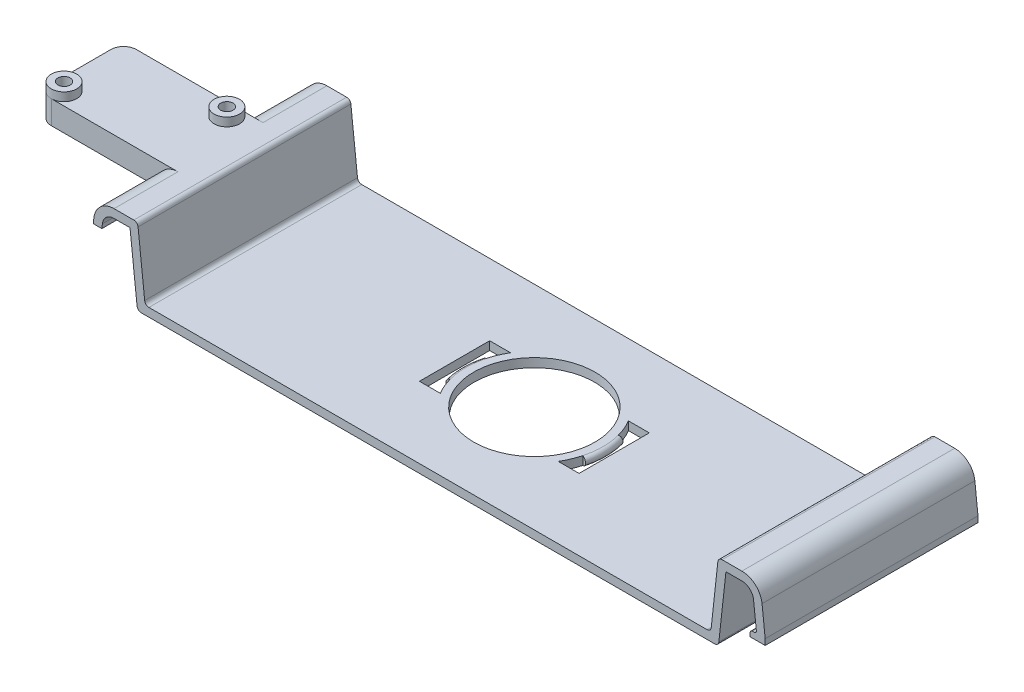
SolidWorks part; units mm, degrees
ref_plane "Front Plane" through (0, 0, 0) normal (0, 0, 1) x (1, 0, 0)
ref_plane "Top Plane" through (0, 0, 0) normal (0, 1, 0) x (1, 0, 0)
ref_plane "Right Plane" through (0, 0, 0) normal (1, 0, 0) x (0, 0, -1)
sketch "Sketch1" plane through (0, 0, 0) normal (0, 0, 1) x (1, 0, 0)
  line L0 (0, 0) -> (-68.25, 0)
  line L1 (55, 0) -> (-55, 0) construction
  line L2 (-68.25, 0) -> (-70, 16)
  line L3 (-70, 16) -> (-73.75, 16)
  line L4 (-76.5, 13.5344) -> (-77.2147, 7)
  line L5 (0, 121.5879) -> (0, -176.7116) construction
  line L6 (0, -55) -> (0, 55) construction
  line L7 (-77.2147, 7) -> (-77.9803, 0) construction
  line L8 (-77.2147, 7) -> (-69.0156, 7) construction
  line L9 (-77.9803, 0) -> (-68.25, 0) construction
  line L10 (0, 2) -> (-66.4568, 2)
  line L11 (-66.4568, 2) -> (-68.2068, 18)
  line L12 (-68.2068, 18) -> (-73.75, 18)
  line L13 (-78.4881, 13.7518) -> (-79.2028, 7.2175)
  line L14 (0, 0) -> (0, 2)
  line L15 (-77.2147, 7) -> (-79.2028, 7.2175)
  arc A0 (-73.75, 16) -> (-76.5, 13.5344) centre (-73.75, 13.2336) ccw
  arc A1 (-73.75, 18) -> (-78.4881, 13.7518) centre (-73.75, 13.2336) ccw
  point P14 (-73.1152, 0)
  point P17 (-73.1152, 7)
  dimension "D1" = 140
  dimension "D2" = 136.5
  dimension "D3" = 16
  dimension "D4" = 3.75
  dimension "D5" = 9
  dimension "D6" = 6.5
  dimension "D7" = 2
extrude "Boss-Extrude1" add sketch "Sketch1" along normal mid plane 50
mirror "Mirror1" about plane through (0, 0, 25) normal (-1, 0, 0) of "Boss-Extrude1"
sketch "Sketch2" plane through (0, 2, 0) normal (0, 1, 0) x (1, 0, 0)
  circle A0 centre (0, 0) radius 14.25
  dimension "D1" = 28.5
extrude "Cut-Extrude1" cut sketch "Sketch2" against normal blind 50 draft 3
sketch "Sketch3" plane through (0, 2, 0) normal (0, 1, 0) x (1, 0, 0)
  line L0 (-18.75, 8.25) -> (-18.75, -8.25)
  line L1 (-18.75, 8.25) -> (-13.8547, 8.25)
  line L3 (-18.75, -8.25) -> (-13.8547, -8.25)
  line L5 (-18.75, 8.25) -> (18.75, -8.25) construction
  line L6 (-18.75, -8.25) -> (-14.7595, -6.4942) construction
  line L7 (18.75, 8.25) -> (18.75, -8.25)
  line L8 (-13.8547, -8.25) -> (13.8547, -8.25) construction
  line L9 (13.8547, -8.25) -> (18.75, -8.25)
  line L10 (-14.7595, -6.4942) -> (0, 0) construction
  line L11 (0, 0) -> (18.75, 8.25) construction
  line L12 (-13.8547, 8.25) -> (13.8547, 8.25) construction
  line L13 (13.8547, 8.25) -> (18.75, 8.25)
  arc A4 (-13.8547, 8.25) -> (-13.8547, -8.25) centre (0, 0) ccw
  arc A5 (13.8547, 8.25) -> (-13.8547, 8.25) centre (0, 0) ccw construction
  arc A6 (-13.8547, -8.25) -> (13.8547, -8.25) centre (0, 0) ccw construction
  arc A7 (13.8547, -8.25) -> (13.8547, 8.25) centre (0, 0) ccw
  point P0 (0, 0)
  dimension "D3" = 32.25
  dimension "D1" = 16.5
  dimension "D2" = 37.5
extrude "Cut-Extrude2" cut sketch "Sketch3" against normal through all
sketch "Sketch4" plane through (0, 0, 0) normal (0, 0, 1) x (1, 0, 0)
  line L0 (16.125, 0) -> (16.125, 2)
  line L1 (17, 1) -> (17, 2.8355) construction
  line L2 (0, 25.7887) -> (0, -14.6472) construction
  line L3 (0, -55) -> (0, 55) construction
  arc A0 (16.125, 2) -> (16.125, 0) centre (15.9911, 1) cw
  dimension "D1" = 34
revolve "Revolve1" add sketch "Sketch4" angle 30 mid plane about axis through (0, 2, 0) along (0, -1, 0)
mirror "Mirror2" about plane through (0, 0, 0) normal (1, 0, 0) of "Revolve1"
fillet "Fillet1" radius 0.2 2 edges at (-70, 16, 0) (70, 16, 0)
fillet "Fillet4" radius 1 6 edges at (-66.4568, 2, 0) (66.4568, 2, 0) (68.25, 0, 0) (-68.25, 0, 0) (68.2068, 18, 0) (-68.2068, 18, 0)
sketch "Sketch6" plane through (0, 0, 0) normal (0, 0, 1) x (1, 0, 0)
  line L0 (79.2266, 7) -> (79.2266, 5.6)
  line L1 (79.2266, 5.6) -> (75.7147, 5.6)
  line L2 (75.7147, 5.6) -> (75.7147, 7)
  line L3 (75.7147, 7) -> (77.2147, 7)
  line L4 (77.2147, 7) -> (79.2028, 7.2175)
  line L5 (79.2028, 7.2175) -> (79.2266, 7)
  line L6 (78.4881, 13.7518) -> (79.2028, 7.2175) construction
  line L7 (77.2147, 7) -> (79.2266, 7) construction
  dimension "D1" = 1.5
  dimension "D2" = 1.4
extrude "Boss-Extrude2" add sketch "Sketch6" along normal up to surface (25 mm away) and the other way up to surface (25 mm away) up to face at (0, 10.6784, 25) other way up to face at (0, 10.6784, -25)
fillet "Fillet5" radius 0.5 2 edges at (75.7147, 7, 0) (77.2147, 7, 0)
sketch "Sketch5" plane through (0, 0, 0) normal (0, 0, 1) x (1, 0, 0)
  line L0 (-73.75, 18) -> (-106.5, 18)
  line L1 (-106.5, 18) -> (-106.5, 7)
  line L2 (-106.5, 7) -> (-77.2147, 7)
  line L3 (-77.2147, 7) -> (-76.5, 13.5344) construction
  line L4 (-77.2147, 7) -> (-76.5, 13.5344)
  line L5 (-73.75, 18) -> (-73.75, 16)
  arc A0 (-73.75, 16) -> (-76.5, 13.5344) centre (-73.75, 13.2336) ccw construction
  arc A1 (-73.75, 16) -> (-76.5, 13.5344) centre (-73.75, 13.2336) ccw
  dimension "D1" = 30
extrude "Boss-Extrude3" add sketch "Sketch5" along normal mid plane 20
sketch "Sketch7" plane through (0, 18, 0) normal (0, 1, 0) x (1, 0, 0)
  line L0 (-11, 0) -> (11, 0) construction
  line L1 (-103.5, 7) -> (-79.25, 7) construction
  line L2 (-103.5, 7) -> (-103.5, -7) construction
  line L3 (-103.5, -7) -> (-79.25, -7) construction
  line L4 (-79.25, 7) -> (-79.25, -7) construction
  line L5 (-103.5, 7) -> (-79.25, -7) construction
  line L6 (-103.5, -7) -> (-79.25, 7) construction
  line L7 (-103.5, -7) -> (-103.5, -10) construction
  line L8 (-73.75, -10) -> (-106.5, -10) construction
  line L9 (-103.5, -7) -> (-106.5, -7) construction
  line L10 (-106.5, -10) -> (-106.5, 10) construction
  circle A0 centre (-79.25, 7) radius 1.45
  circle A1 centre (-103.5, -7) radius 1.45
  point P0 (-91.375, 0)
  dimension "D3" = 2.9
  dimension "D1" = 24.25
  dimension "D2" = 14
extrude "Cut-Extrude3" cut sketch "Sketch7" against normal through all
sketch "Sketch9" plane through (0, 18, 0) normal (0, 1, 0) x (1, 0, 0)
  line L0 (-73.75, -10) -> (-106.5, -10) construction
  circle A0 centre (-79.25, 7) radius 3
  circle A1 centre (-103.5, -7) radius 3
  circle A2 centre (-103.5, -7) radius 1.45 construction
  circle A3 centre (-79.25, 7) radius 1.45 construction
  circle A4 centre (-103.5, -7) radius 1.45
  circle A5 centre (-79.25, 7) radius 1.45
extrude "Boss-Extrude5" add sketch "Sketch9" along normal blind 2
fillet "Fillet6" radius 3 2 edges at (-106.5, 12.5, 10) (-106.5, 12.5, -10)
sketch "Sketch10" plane through (0, 0, 0) normal (0, 0, 1) x (1, 0, 0)
  line L0 (-77.2147, 7) -> (-76.5, 13.5344) construction
  line L3 (-106.5, 7) -> (-76.6131, 7)
  line L4 (-106.5, 7) -> (-106.5, 12.5)
  line L5 (-106.5, 12.5) -> (-76.6131, 12.5)
  line L6 (-76.6131, 7) -> (-76.6131, 12.5)
  line L7 (-100.5, 20) -> (-106.5, 20) construction
  dimension "D1" = 7.5
extrude "Cut-Extrude4" cut sketch "Sketch10" against normal through all both and the other way through all
